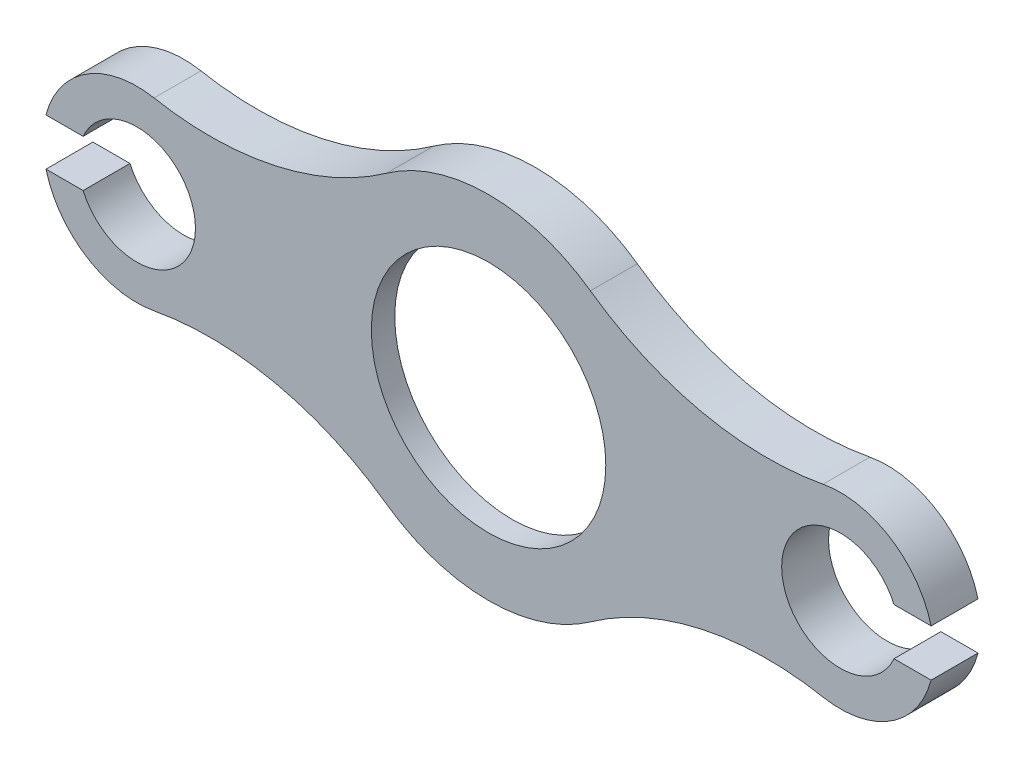
SolidWorks part; units mm, degrees
material "AISI 1020"
ref_plane "Plan de face" through (0, 0, 0) normal (0, 0, 1) x (1, 0, 0)
ref_plane "Plan de dessus" through (0, 0, 0) normal (0, 1, 0) x (1, 0, 0)
ref_plane "Plan de droite" through (0, 0, 0) normal (1, 0, 0) x (0, 0, -1)
sketch "Esquisse1" plane through (0, 0, 0) normal (0, 0, 1) x (1, 0, 0)
  line L0 (-150, 0) -> (150, 0) construction
  line L1 (0, -88.7998) -> (0, 88.7998) construction
  line L2 (172.9129, 10) -> (188.7298, 10)
  line L3 (172.9129, -10) -> (188.7298, -10)
  line L4 (-172.9129, -10) -> (-188.7298, -10)
  line L5 (-172.9129, 10) -> (-188.7298, 10)
  circle A0 centre (0, 0) radius 50
  circle A1 centre (0, 0) radius 67.8
  arc A2 (172.9129, 10) -> (172.9129, -10) centre (150, 0) ccw
  arc A3 (188.7298, 10) -> (142.6546, 39.3198) centre (150, 0) ccw
  arc A4 (43.4353, 61.1422) -> (-43.4353, 61.1422) centre (0, 0) ccw
  arc A5 (43.4353, 61.1422) -> (142.6546, 39.3198) centre (118.768, 167.1851) ccw
  arc A6 (43.4353, -61.1422) -> (142.6546, -39.3198) centre (118.768, -167.1851) cw
  arc A7 (142.6546, -39.3198) -> (188.7298, -10) centre (150, 0) ccw
  arc A8 (-142.6546, -39.3198) -> (-188.7298, -10) centre (-150, 0) cw
  arc A9 (-43.4353, -61.1422) -> (-142.6546, -39.3198) centre (-118.768, -167.1851) ccw
  arc A10 (-43.4353, 61.1422) -> (-142.6546, 39.3198) centre (-118.768, 167.1851) cw
  arc A11 (-188.7298, 10) -> (-142.6546, 39.3198) centre (-150, 0) cw
  arc A12 (-172.9129, 10) -> (-172.9129, -10) centre (-150, 0) cw
  arc A13 (-43.4353, -61.1422) -> (43.4353, -61.1422) centre (0, 0) ccw
  point P4 (0, 0)
  point P8 (0, 0)
  dimension "D2" = 100
  dimension "D3" = 135.6
  dimension "D4" = 50
  dimension "D5" = 80
  dimension "D6" = 150
  dimension "D1" = 150
  dimension "D7" = 10
extrude "Boss.-Extru.1" add sketch "Esquisse1" along normal blind 20 contours A9 A13 A6 A7 L3 A2 L2 A3 A5 A4 A10 A11 L5 A12 L4 A8 A1 region at (120.9383, 0, 0)
extrude "Boss.-Extru.3" add sketch "Esquisse1<4>" along normal blind 10 from offset 10 contours A1 A0 region at (-65.8823, 0, 0)
sketch "Esquisse1<4>" plane through (0, 0, 0) normal (0, 0, 1) x (1, 0, 0) same geometry as "Esquisse1"
